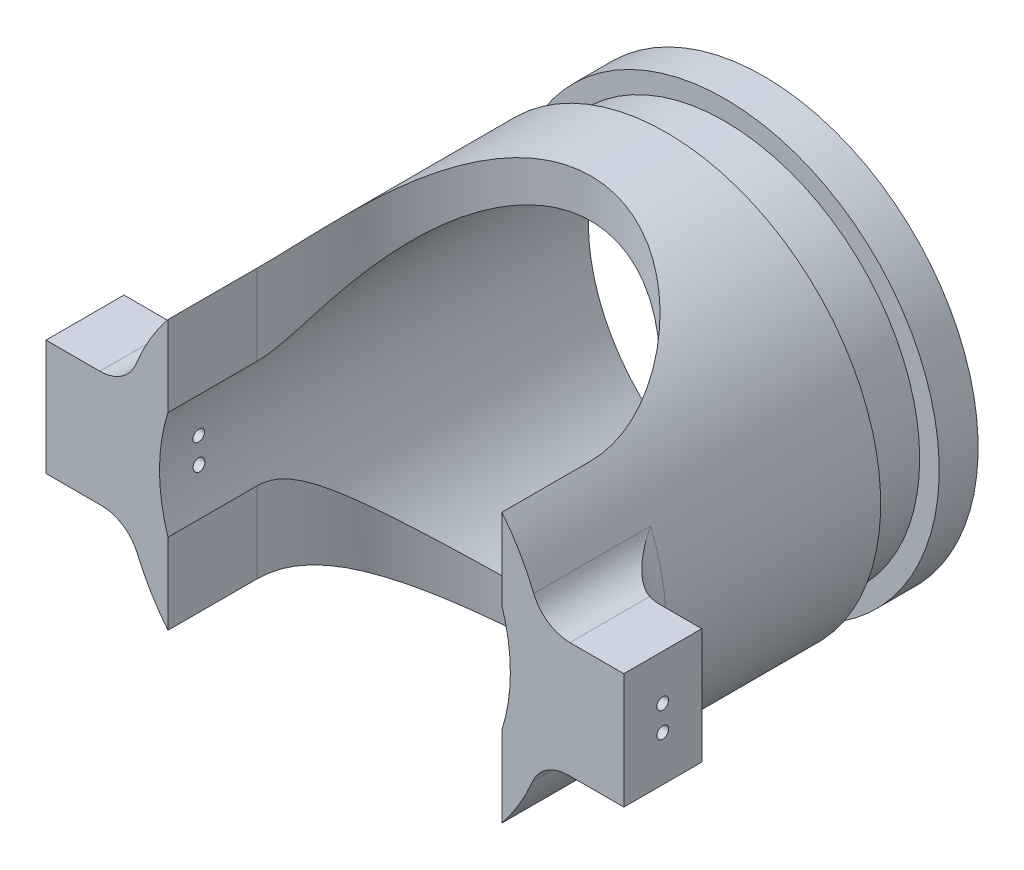
SolidWorks part; units mm, degrees
ref_plane "Front Plane" through (0, 0, 0) normal (0, 0, 1) x (1, 0, 0)
ref_plane "Top Plane" through (0, 0, 0) normal (0, 1, 0) x (1, 0, 0)
ref_plane "Right Plane" through (0, 0, 0) normal (1, 0, 0) x (0, 0, -1)
sketch "Sketch3" plane through (0, 0, 0) normal (0, 1, 0) x (1, 0, 0)
  line L0 (0, 54.7941) -> (0, -55.0743) construction
  line L1 (0, -55) -> (0, 55) construction
  line L2 (-55, 14.7941) -> (-55, 4.7941)
  line L3 (-55, 4.7941) -> (-50, 4.7941)
  line L4 (-50, 4.7941) -> (-50, -10.2059)
  line L5 (-50, -10.2059) -> (-55, -10.2059)
  line L6 (-55, -10.2059) -> (-55, -95.2059)
  line L7 (-55, -95.2059) -> (-45, -95.2059)
  line L8 (-45, -95.2059) -> (-45, 14.7941)
  line L9 (-45, 14.7941) -> (-55, 14.7941)
  dimension "D1" = 10
  dimension "D2" = 15
  dimension "D3" = 5
  dimension "D4" = 110
  dimension "D5" = 45
  dimension "D6" = 10
  dimension "D7" = 10
revolve "Revolve1" add sketch "Sketch3" angle 360 about L0
sketch "Sketch4" plane through (0, 0, 95.2059) normal (0, 0, 1) x (1, 0, 0)
  line L0 (0, 0) -> (54.9974, -0.5318) construction
  line L1 (52.8195, -15.333) -> (74.1061, -15.333)
  line L2 (53.1061, 14.3087) -> (74.1061, 14.3087)
  line L3 (74.1061, 14.3087) -> (74.1061, -15.333)
  line L4 (0, 0) -> (0, -68.7487) construction
  line L5 (-74.1061, 14.3087) -> (-74.1061, -15.333)
  line L6 (-53.1061, 14.3087) -> (-74.1061, 14.3087)
  line L7 (-52.8195, -15.333) -> (-74.1061, -15.333)
  arc A0 (53.1061, 14.3087) -> (52.8195, -15.333) centre (0, 0) cw
  circle A1 centre (0, 0) radius 55 construction
  arc A2 (-53.1061, 14.3087) -> (-52.8195, -15.333) centre (0, 0) ccw
  dimension "D1" = 21
extrude "Boss-Extrude1" add sketch "Sketch4" against normal blind 20
sketch "Sketch6" plane through (0, 0, 0) normal (0, 1, 0) x (1, 0, 0)
  line L0 (0, -134.2822) -> (0, -72.3565) construction
  line L1 (0, -55) -> (0, 55) construction
  line L2 (-42.8195, -134.2822) -> (-42.8195, -72.3565)
  line L3 (42.8195, -134.2822) -> (42.8195, -72.3565)
  line L4 (-52.8195, -75.2059) -> (-52.8195, -95.2059) construction
  arc A0 (-42.8195, -134.2822) -> (42.8195, -134.2822) centre (0, -134.2822) ccw
  arc A1 (42.8195, -72.3565) -> (-42.8195, -72.3565) centre (0, -72.3565) ccw
  point P5 (0, -103.3194)
  dimension "D1" = 10
extrude "Cut-Extrude1" cut sketch "Sketch6" against normal mid plane 130
fillet "Fillet2" radius 10 4 edges at (-52.8195, -15.333, 85.2059) (52.8195, -15.333, 85.2059) (54.9974, -0.5318, 75.2059) (53.1061, 14.3087, 85.2059)
fillet "Fillet3" radius 10 2 edges at (-54.8707, -3.769, 75.2059) (-53.1061, 14.3087, 85.2059)
sketch "Sketch7" plane through (-74.1061, 0, 0) normal (-1, 0, 0) x (0, 0, 1)
  line L0 (75.2059, -0.5121) -> (95.2059, -0.5121) construction
  line L1 (75.2059, 14.3087) -> (75.2059, -15.333) construction
  line L2 (95.2059, 14.3087) -> (95.2059, -15.333) construction
  circle A0 centre (85.2272, -3.7419) radius 1.5
  circle A1 centre (85.2272, 2.7177) radius 1.5
  dimension "D1" = 3
extrude "Cut-Extrude2" cut sketch "Sketch7" against normal through all
